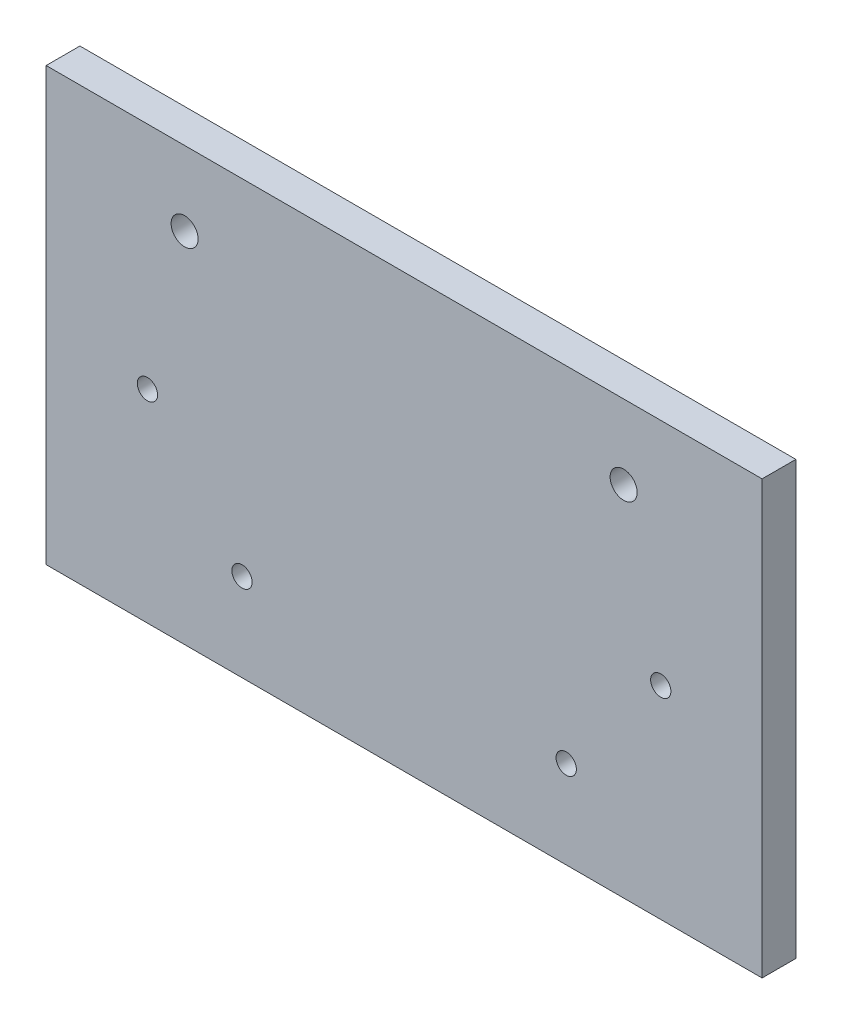
SolidWorks part; units mm, degrees
ref_plane "Front" through (0, 0, 0) normal (0, 0, 1) x (1, 0, 0)
ref_plane "Top" through (0, 0, 0) normal (0, 1, 0) x (1, 0, 0)
ref_plane "Right" through (0, 0, 0) normal (1, 0, 0) x (0, 0, -1)
sketch "Sketch1" plane through (0, 0, 0) normal (0, 0, 1) x (1, 0, 0)
  line L1 (-53, 32) -> (53, 32)
  line L2 (-53, 32) -> (-53, -32)
  line L3 (-53, -32) -> (53, -32)
  line L4 (53, 32) -> (53, -32)
  line L5 (-53, 32) -> (53, -32) construction
  line L6 (-53, -32) -> (53, 32) construction
  point P0 (0, 0)
  dimension "D1" = 64
  dimension "D2" = 106
extrude "Boss-Extrude1" add sketch "Sketch1" along normal blind 5
sketch "Sketch2" plane through (0, 0, 0) normal (0, 0, 1) x (1, 0, 0)
  line L0 (-53, -32) -> (53, -32) construction
  line L1 (0, 32) -> (0, -32) construction
  line L2 (53, 32) -> (-53, 32) construction
  circle A0 centre (-24, -19) radius 1.5
  circle A1 centre (24, -19) radius 1.5
  circle A2 centre (-38, -2) radius 1.5
  circle A3 centre (38, -2) radius 1.5
  circle A4 centre (-32.5, 21) radius 2
  circle A5 centre (32.5, 21) radius 2
  dimension "D1" = 3
  dimension "D2" = 3
  dimension "D6" = 3
  dimension "D7" = 3
  dimension "D11" = 4
  dimension "D12" = 4
  dimension "D3" = 13
  dimension "D4" = 48
  dimension "D5" = 24
  dimension "D8" = 76
  dimension "D9" = 38
  dimension "D10" = 30
  dimension "D13" = 11
  dimension "D14" = 65
  dimension "D15" = 32.5
extrude "Cut-Extrude2" cut sketch "Sketch2" along normal through all
equation "\"D5@Sketch2\"= \"D4@Sketch2\" / 2"
equation "\"D9@Sketch2\"= \"D8@Sketch2\" / 2"
equation "\"D15@Sketch2\"= \"D14@Sketch2\" / 2"
